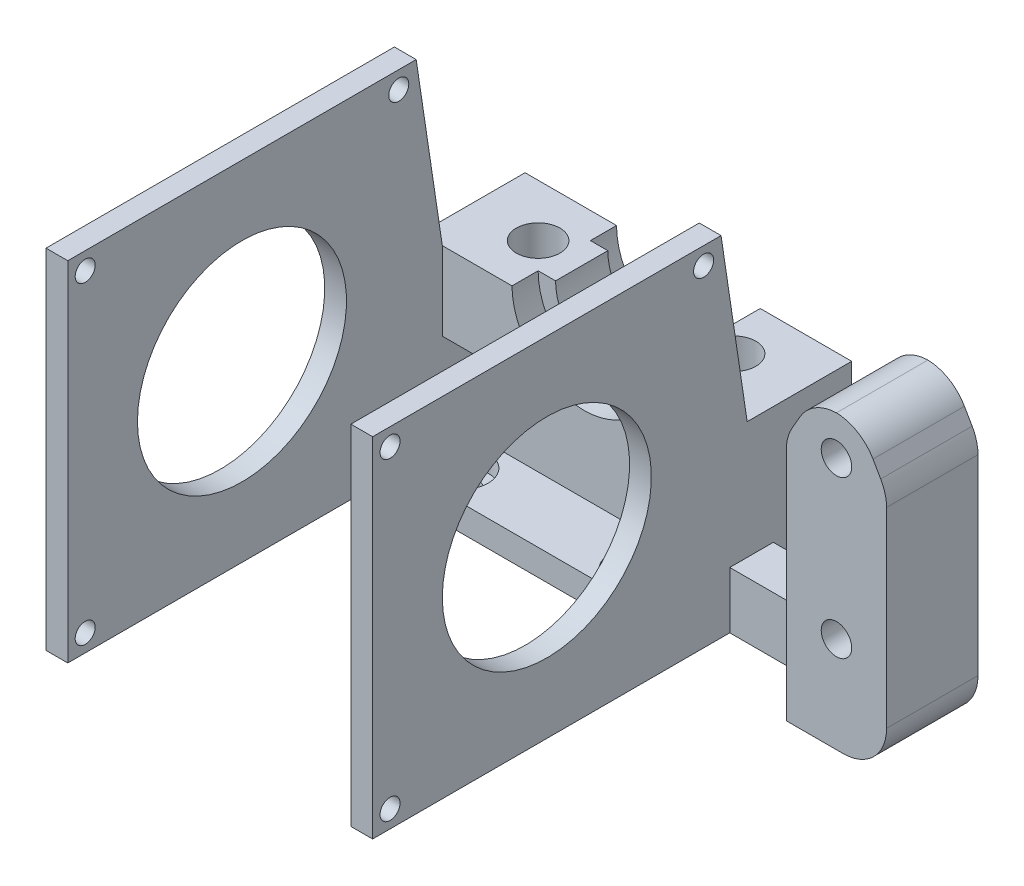
SolidWorks part; units mm, degrees
ref_plane "Front Plane" through (0, 0, 0) normal (0, 0, 1) x (1, 0, 0)
ref_plane "Top Plane" through (0, 0, 0) normal (0, 1, 0) x (1, 0, 0)
ref_plane "Right Plane" through (0, 0, 0) normal (1, 0, 0) x (0, 0, -1)
sketch "Sketch1" plane through (0, 0, 0) normal (0, 1, 0) x (1, 0, 0)
  line L1 (-22.5, -13.5) -> (22.5, -13.5)
  line L2 (-22.5, -13.5) -> (-22.5, 13.5)
  line L3 (-22.5, 13.5) -> (22.5, 13.5)
  line L4 (22.5, -13.5) -> (22.5, 13.5)
  line L5 (-22.5, -13.5) -> (22.5, 13.5) construction
  line L6 (-22.5, 13.5) -> (22.5, -13.5) construction
  point P0 (0, 0)
  dimension "D1" = 27
  dimension "D2" = 45
extrude "Boss-Extrude1" add sketch "Sketch1" along normal blind 3
sketch "Sketch2" plane through (0, 3, 0) normal (0, 1, 0) x (1, 0, 0)
  line L0 (0, 13.5) -> (0, -13.5) construction
  line L1 (22.5, 13.5) -> (-22.5, 13.5) construction
  line L2 (-22.5, -13.5) -> (22.5, -13.5) construction
  line L3 (-22.5, 0) -> (22.5, 0) construction
  line L4 (-22.5, 13.5) -> (-22.5, -13.5) construction
  line L5 (22.5, -13.5) -> (22.5, 13.5) construction
  circle A0 centre (-10, 10) radius 1.75
  circle A1 centre (10, 10) radius 1.75
  circle A2 centre (10, -10) radius 1.75
  circle A3 centre (-10, -10) radius 1.75
  dimension "D1" = 3.5
  dimension "D2" = 10
  dimension "D3" = 10
extrude "Cut-Extrude1" cut sketch "Sketch2" against normal up to next
sketch "Sketch3" plane through (0, 3, 0) normal (0, 1, 0) x (1, 0, 0)
  line L0 (0, 13.5) -> (0, -13.5) construction
  line L1 (22.5, 13.5) -> (-22.5, 13.5) construction
  line L2 (-22.5, -13.5) -> (22.5, -13.5) construction
  line L3 (-22.5, 0) -> (22.5, 0) construction
  line L4 (-22.5, 13.5) -> (-22.5, -13.5) construction
  line L5 (22.5, -13.5) -> (22.5, 13.5) construction
  circle A0 centre (-10, 10) radius 3
  circle A1 centre (10, 10) radius 3
  circle A2 centre (10, -10) radius 3
  circle A3 centre (-10, -10) radius 3
  dimension "D1" = 6
extrude "Cut-Extrude2" cut sketch "Sketch3" against normal blind 2
ref_plane "Plane1" through (0, 0, 0) normal (0, 0, 1) x (1, 0, 0)
sketch "Sketch5" plane through (0, 0, 0) normal (0, 0, 1) x (1, 0, 0)
  line L0 (0, 0) -> (0, 20) construction
  line L1 (22.5, 3) -> (-22.5, 3) construction
  line L2 (16.25, 3) -> (-16.25, 3)
  line L3 (-16.25, 3) -> (-16.25, 20)
  line L4 (-16.25, 20) -> (-6.25, 20)
  line L5 (16.25, 20) -> (6.25, 20)
  line L6 (16.25, 3) -> (16.25, 20)
  arc A0 (-6.25, 20) -> (6.25, 20) centre (0, 20) ccw
  point P13 (0, 3)
  dimension "D3" = 12.5
  dimension "D1" = 17
  dimension "D2" = 10
extrude "Boss-Extrude2" add sketch "Sketch5" along normal mid plane 12
sketch "Sketch12" plane through (0, 0, 0) normal (0, 0, 1) x (1, 0, 0)
  circle A0 centre (0, 20) radius 8.25
  dimension "D1" = 16.5
extrude "Cut-Extrude6" cut sketch "Sketch12" against normal up to next from offset 3 offset against normal yes
mirror "Mirror1" about plane through (0, 0, 0) normal (0, 0, 1) of "Cut-Extrude6"
sketch "Sketch15" plane through (0, 20, 0) normal (0, 1, 0) x (1, 0, 0)
  line L0 (-16.25, 0) -> (-6.25, 0) construction
  line L1 (-16.25, -6) -> (-16.25, 6) construction
  line L2 (-6.25, -3) -> (-6.25, 3) construction
  line L3 (0, 6) -> (0, -6) construction
  line L4 (8.25, 6) -> (-8.25, 6) construction
  line L5 (-16.25, -6) -> (16.25, -6) construction
  circle A0 centre (-11.25, 0) radius 2.5
  circle A1 centre (11.25, 0) radius 2.5
  dimension "D1" = 5
extrude "Cut-Extrude7" cut sketch "Sketch15" against normal blind 6
sketch "Sketch16" plane through (-16.25, 0, 0) normal (-1, 0, 0) x (0, 0, 1)
  line L0 (6, 20) -> (56, 20) construction
  line L1 (9, 3) -> (9, 0)
  line L2 (49, 40) -> (9, 40)
  line L3 (49, 40) -> (49, 0)
  line L4 (49, 0) -> (9, 0)
  line L6 (49, 40) -> (9, 0) construction
  line L7 (49, 0) -> (9, 40) construction
  line L8 (-6, 3) -> (9, 3)
  line L9 (-6, 3) -> (-6, 20)
  line L10 (6, 40) -> (9, 40)
  line L11 (6, 20) -> (6, 40)
  line L12 (6, 20) -> (-6, 20)
  circle A0 centre (47, 2) radius 1.15
  circle A1 centre (47, 38) radius 1.15
  circle A2 centre (11, 38) radius 1.15
  circle A3 centre (29, 20) radius 12
  point P3 (29, 20)
  dimension "D7" = 18
  dimension "D8" = 2.3
  dimension "D9" = 24
  dimension "D1" = 50
  dimension "D2" = 40
  dimension "D3" = 40
  dimension "D4" = 7
  dimension "D5" = 40
  dimension "D6" = 3
extrude "Boss-Extrude5" add sketch "Sketch16" along normal blind 2.5
sketch "Sketch17" plane through (-22.5, 0, 0) normal (-1, 0, 0) x (0, 0, 1)
  line L0 (-13.5, 0) -> (13.5, 0) construction
  line L1 (13.5, 3) -> (8, 3)
  line L2 (13.5, 3) -> (13.5, 0)
  line L3 (13.5, 0) -> (8, 0)
  line L4 (8, 3) -> (8, 0)
  line L5 (49, 0) -> (49, 40) construction
  dimension "D1" = 41
extrude "Cut-Extrude8" cut sketch "Sketch17" against normal up to surface (3.75 mm away) and the other way through all up to face at (-18.75, 2, 48.15)
mirror "Mirror2" about plane through (0, 0, 0) normal (1, 0, 0) of "Boss-Extrude5", "Cut-Extrude8"
sketch "Sketch18" plane through (0, 0, -6) normal (0, 0, -1) x (-1, 0, 0)
  line L0 (-18.75, 20) -> (-36.5, 20) construction
  line L2 (-36.5, 33.5) -> (-36.5, 6.5) construction
  line L3 (-42.25, 33.5) -> (-30.75, 33.5)
  line L4 (-42.25, 33.5) -> (-42.25, 6.5)
  line L6 (-30.75, 33.5) -> (-30.75, 6.5)
  line L7 (-42.25, 33.5) -> (-30.75, 6.5) construction
  line L8 (-42.25, 6.5) -> (-30.75, 33.5) construction
  line L10 (-30.75, 6.5) -> (-18.75, 6.5)
  line L12 (-42.25, 6.5) -> (-42.25, 0)
  line L13 (-42.25, 0) -> (-18.75, 0)
  line L14 (-18.75, 6.5) -> (-18.75, 0)
  line L15 (-42.25, 6.5) -> (-30.75, 6.5) construction
  circle A0 centre (-36.5, 29) radius 1.75
  circle A1 centre (-36.5, 11) radius 1.75
  point P3 (-16.25, 20)
  point P4 (-18.75, 20)
  dimension "D4" = 3.5
  dimension "D5" = 9
  dimension "D1" = 12
  dimension "D2" = 11.5
  dimension "D3" = 27
  dimension "D6" = 12
extrude "Boss-Extrude6" add sketch "Sketch18" against normal blind 5 from offset 9 offset against normal yes
ref_plane "Plane2" through (0, 0, 56) normal (0, 0, 1) x (1, 0, 0)
sketch "Sketch21" plane through (0, 0, 8) normal (0, 0, 1) x (1, 0, 0)
  line L0 (18.75, 0) -> (42.25, 0) construction
  line L1 (42.25, 33.5) -> (30.75, 33.5)
  line L2 (42.25, 33.5) -> (42.25, 0)
  line L3 (42.25, 0) -> (30.75, 0)
  line L4 (30.75, 33.5) -> (30.75, 0)
  circle A0 centre (36.5, 29) radius 1.75
  circle A2 centre (36.5, 11) radius 1.75
  dimension "D2" = 3.5
  dimension "D4" = 18
  dimension "D1" = 11.5
  dimension "D3" = 2
extrude "Boss-Extrude7" add sketch "Sketch21" along normal blind 5.5
sketch "Sketch19" plane through (0, 0, 3) normal (0, 0, -1) x (-1, 0, 0)
  line L0 (-39.8486, 11) -> (-38.1743, 8.1)
  line L1 (-39.8486, 29) -> (-38.1743, 26.1)
  line L2 (-38.1743, 26.1) -> (-34.8257, 26.1)
  line L3 (-34.8257, 26.1) -> (-33.1514, 29)
  line L4 (-33.1514, 29) -> (-34.8257, 31.9)
  line L5 (-34.8257, 31.9) -> (-38.1743, 31.9)
  line L6 (-38.1743, 31.9) -> (-39.8486, 29)
  line L7 (-38.1743, 8.1) -> (-34.8257, 8.1)
  line L8 (-34.8257, 8.1) -> (-33.1514, 11)
  line L9 (-33.1514, 11) -> (-34.8257, 13.9)
  line L10 (-34.8257, 13.9) -> (-38.1743, 13.9)
  line L11 (-38.1743, 13.9) -> (-39.8486, 11)
  circle A0 centre (-36.5, 29) radius 2.9 construction
  dimension "D1" = 5.8
  dimension "D2" = 2.9
  dimension "D4" = 18
  dimension "D3" = 2
extrude "Cut-Extrude9" cut sketch "Sketch19" against normal blind 2
chamfer "Chamfer1" distance 3 angle 60 2 edges at (42.25, 33.5, 8.25) (30.75, 33.5, 8.25)
fillet "Fillet1" radius 5 5 edges at (42.25, 0, 8.25) (42.25, 28.3038, 8.25) (30.75, 28.3038, 8.25) (39.25, 33.5, 8.25) (33.75, 33.5, 8.25)
sketch "Sketch20" plane through (0, 0, 6) normal (0, 0, 1) x (1, 0, 0)
  line L0 (0, 0) -> (0, 11.75) construction
  line L1 (-16.25, 3) -> (-12.25, 3)
  line L2 (-16.25, 3) -> (-16.25, 11)
  line L3 (-16.25, 11) -> (-12.25, 11)
  line L4 (-12.25, 3) -> (-12.25, 11)
  line L5 (16.25, 11) -> (12.25, 11)
  line L6 (12.25, 3) -> (12.25, 11)
  line L7 (16.25, 3) -> (12.25, 3)
  line L8 (16.25, 3) -> (16.25, 11)
  arc A0 (-8.25, 20) -> (8.25, 20) centre (0, 20) ccw construction
  dimension "D1" = 4
  dimension "D2" = 8
extrude "Cut-Extrude10" cut sketch "Sketch20" against normal up to next and the other way through all
chamfer "Chamfer2" distance 3 distance2 20 1 edges at (-17.5, 40, 6)
chamfer "Chamfer3" distance 20 distance2 3 1 edges at (17.5, 40, 6)
